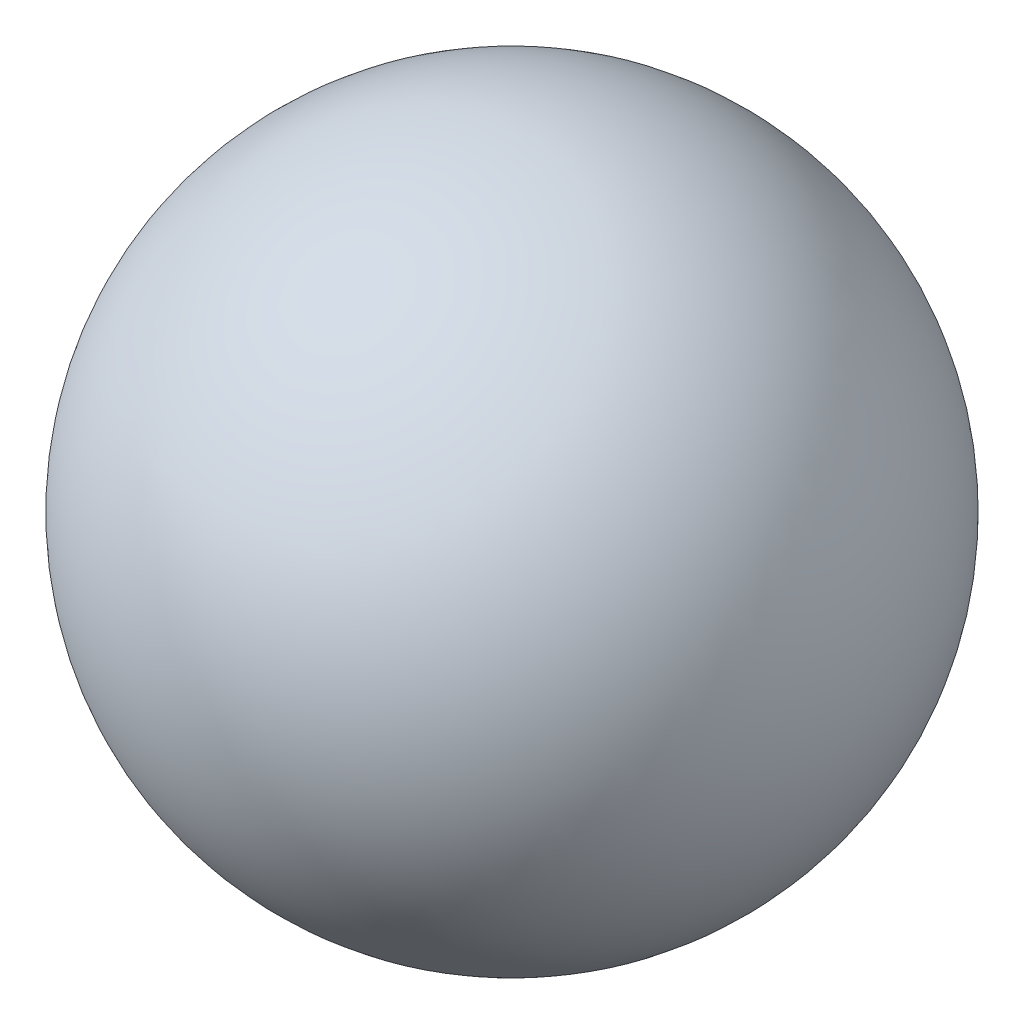
SolidWorks part; units mm, degrees
material "Plain Carbon Steel"
ref_plane "Front Plane" through (0, 0, 0) normal (0, 0, 1) x (1, 0, 0)
ref_plane "Top Plane" through (0, 0, 0) normal (0, 1, 0) x (1, 0, 0)
ref_plane "Right Plane" through (0, 0, 0) normal (1, 0, 0) x (0, 0, -1)
sketch "Sketch1" plane through (0, 0, 0) normal (0, 0, 1) x (1, 0, 0)
  line L0 (0, -2.4) -> (0, 2.4) construction
  line L1 (0, 2.4) -> (0, -2.4)
  arc A0 (0, -2.4) -> (0, 2.4) centre (0, 0) ccw
  dimension "D1" = 2.4
revolve "Revolve1" add sketch "Sketch1" angle 360 about L0
ref_axis "Axis1" through (0, 0, -2.64) along (0, 0, 1)
